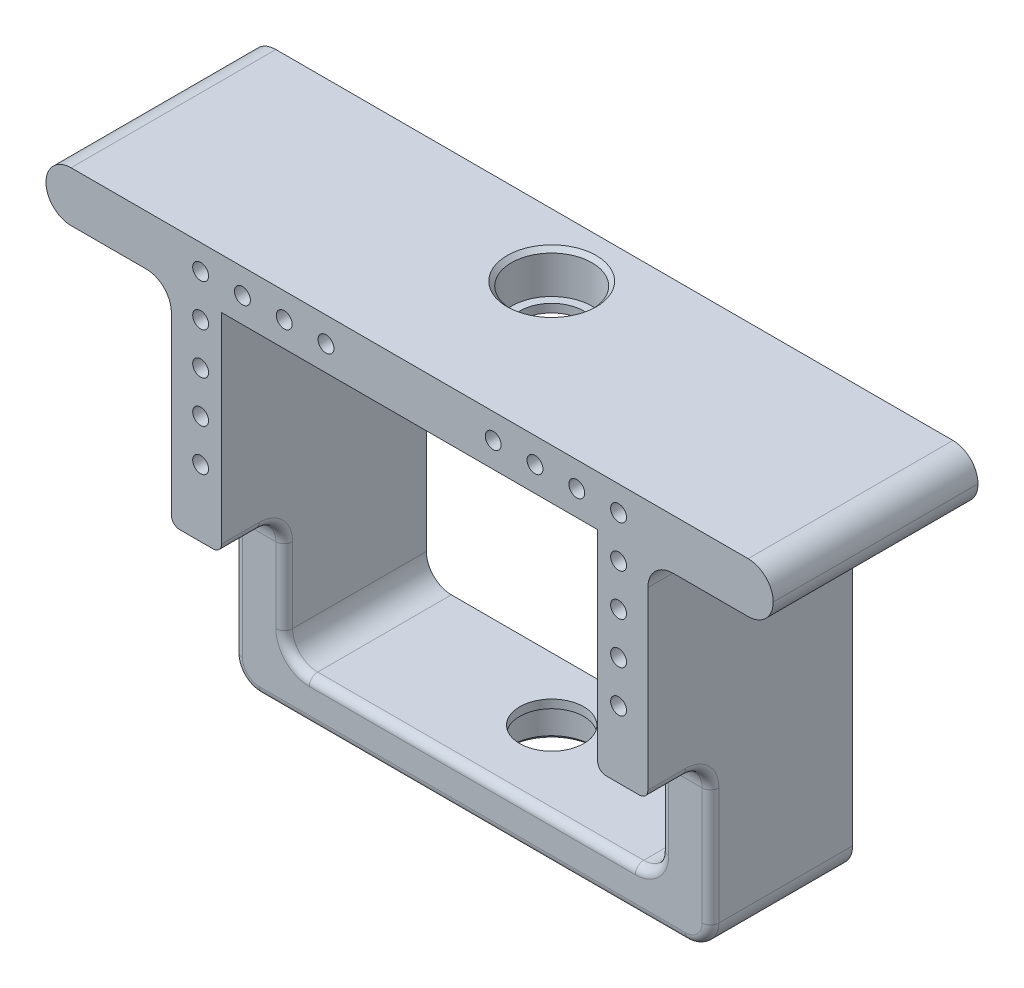
SolidWorks part; units mm, degrees
ref_plane "Plan de face" through (0, 0, 0) normal (0, 0, 1) x (1, 0, 0)
ref_plane "Plan de dessus" through (0, 0, 0) normal (0, 1, 0) x (1, 0, 0)
ref_plane "Plan de droite" through (0, 0, 0) normal (1, 0, 0) x (0, 0, -1)
sketch "Esquisse1" plane through (0, 0, 0) normal (0, 0, 1) x (1, 0, 0)
  line L1 (0, 0) -> (114, 0)
  line L2 (0, 0) -> (0, -102)
  line L3 (0, -102) -> (114, -102)
  line L4 (114, 0) -> (114, -102)
  line L5 (12, -12) -> (102, -12)
  line L6 (12, -12) -> (12, -92)
  line L7 (12, -92) -> (102, -92)
  line L8 (102, -12) -> (102, -92)
  dimension "D1" = 80
  dimension "D2" = 12
  dimension "D3" = 12
  dimension "D4" = 12
  dimension "D5" = 10
  dimension "D6" = 90
extrude "Boss.-Extru.1" add sketch "Esquisse1" along normal blind 49
sketch "Esquisse2" plane through (0, 0, 49) normal (0, 0, 1) x (1, 0, 0)
  line L0 (114, -102) -> (114, 0) construction
  line L1 (0, -102) -> (114, -102)
  line L2 (0, -102) -> (0, -62)
  line L3 (0, -62) -> (114, -62)
  line L4 (114, -102) -> (114, -62)
  dimension "D1" = 40
extrude "Enlèv. mat.-Extru.1" cut sketch "Esquisse2" against normal blind 15
sketch "Esquisse3" plane through (0, 0, 49) normal (0, 0, 1) x (1, 0, 0)
  line L0 (57, 0) -> (57, -12) construction
  line L1 (114, 0) -> (0, 0) construction
  line L2 (102, -12) -> (12, -12) construction
  line L3 (-28.1553, -6) -> (136.1205, -6) construction
  circle A0 centre (57, -6) radius 1.9 construction
  circle A1 centre (67, -6) radius 1.9 construction
  circle A2 centre (77, -6) radius 1.9
  circle A3 centre (87, -6) radius 1.9
  circle A4 centre (97, -6) radius 1.9
  circle A5 centre (107, -6) radius 1.9
  circle A6 centre (47, -6) radius 1.9 construction
  circle A7 centre (37, -6) radius 1.9
  circle A8 centre (27, -6) radius 1.9
  circle A9 centre (17, -6) radius 1.9
  circle A10 centre (7, -6) radius 1.9
  circle A11 centre (7, -16) radius 1.9
  circle A12 centre (107, -16) radius 1.9
  circle A13 centre (7, -26) radius 1.9
  circle A14 centre (107, -26) radius 1.9
  circle A15 centre (7, -36) radius 1.9
  circle A16 centre (107, -36) radius 1.9
  circle A17 centre (7, -46) radius 1.9
  circle A18 centre (107, -46) radius 1.9
  point P8 (57, -6)
  dimension "D1" = 3.8
  dimension "D2" = 6
  dimension "D3" = 6
  dimension "D4" = 5
extrude "Enlèv. mat.-Extru.2" cut sketch "Esquisse3" against normal through all
sketch "Esquisse4" plane through (0, 0, 0) normal (0, 0, -1) x (-1, 0, 0)
  circle A0 centre (-107, -6) radius 4
  circle A1 centre (-87, -6) radius 4
  circle A2 centre (-67, -6) radius 4 construction
  circle A3 centre (-47, -6) radius 4 construction
  circle A4 centre (-27, -6) radius 4
  circle A5 centre (-7, -6) radius 4
  circle A6 centre (-87, -26) radius 4
  circle A7 centre (-67, -26) radius 4
  circle A8 centre (-47, -26) radius 4
  circle A9 centre (-27, -26) radius 4
  circle A10 centre (-7, -26) radius 4
  circle A11 centre (-87, -46) radius 4
  circle A12 centre (-67, -46) radius 4
  circle A13 centre (-47, -46) radius 4
  circle A14 centre (-27, -46) radius 4
  circle A15 centre (-7, -46) radius 4
  circle A16 centre (-107, -26) radius 4
  circle A17 centre (-107, -46) radius 4
  circle A18 centre (-87, -6) radius 1.9 construction
  circle A19 centre (-107, -26) radius 1.9 construction
  point P3 (0, 0)
  dimension "D1" = 8
  dimension "D2" = 6
  dimension "D3" = 3
extrude "Enlèv. mat.-Extru.3" cut sketch "Esquisse4" against normal offset from surface (39 mm away) 10 up to face at (88.9, -6, 49)
sketch "Esquisse5" plane through (0, 0, 0) normal (0, 0, -1) x (-1, 0, 0)
  line L0 (-12, -12) -> (-102, -12) construction
  line L1 (0, 0) -> (30, 0)
  line L2 (0, 0) -> (0, -12)
  line L3 (0, -12) -> (30, -12)
  line L4 (30, 0) -> (30, -12)
  line L5 (-114, 0) -> (-144, 0)
  line L6 (-114, 0) -> (-114, -12)
  line L7 (-114, -12) -> (-144, -12)
  line L8 (-144, 0) -> (-144, -12)
  dimension "D1" = 30
  dimension "D2" = 30
extrude "Boss.-Extru.2" add sketch "Esquisse5" against normal up to vertex (49 mm away) up to point (0, 0, 49)
sketch "Esquisse6" plane through (0, 0, 0) normal (0, 1, 0) x (1, 0, 0)
  line L0 (-30, -15) -> (144, -15) construction
  line L1 (-30, -49) -> (-30, 0) construction
  line L2 (144, -49) -> (144, 0) construction
  line L3 (144, -49) -> (-30, -49) construction
  line L4 (57, -49) -> (57, 0) construction
  line L5 (0, 0) -> (114, 0) construction
  circle A0 centre (57, -15) radius 7.65
  dimension "D2" = 15.3
  dimension "D1" = 34
extrude "Enlèv. mat.-Extru.4" cut sketch "Esquisse6" against normal through all
sketch "Esquisse7" plane through (0, 0, 0) normal (0, 1, 0) x (1, 0, 0)
  circle A0 centre (57, -15) radius 9.65
  dimension "D1" = 19.3
extrude "Enlèv. mat.-Extru.5" cut sketch "Esquisse7" against normal offset from surface (10 mm away) 2 up to face at (57, -12, 7.35)
extrude "Enlèv. mat.-Extru.6" cut sketch "Esquisse7<2>" along normal offset from surface (8 mm away) 2 from surface up to face at (57, -92, 22.65) starting at face at (57, -102, 22.65)
sketch "Esquisse7<2>" plane through (0, 0, 0) normal (0, 1, 0) x (1, 0, 0) same geometry as "Esquisse7"
fillet "Congé1" radius 6 12 edges at (144, -12, 24.5) (144, 0, 24.5) (-30, 0, 24.5) (-30, -12, 24.5) (0, -102, 17) (12, -92, 17) (102, -92, 17) (114, -102, 17) (114, -12, 24.5) (6, -62, 34) (108, -62, 34) (0, -12, 24.5)
chamfer "Chanfrein1" distance 1 angle 45 2 edges at (57, -102, 24.65) (57, 0, 24.65)
sketch "Esquisse8" plane through (0, -102, 0) normal (0, -1, 0) x (1, 0, 0)
  text T0 "IUT GEII Toulon - Robot Club Toulonnais" font "Century Gothic" height 3.75
  point P1 (9.7545, 26.8213)
  point P2 (0, 0)
  point P3 (0, 0)
  point P4 (10.6614, 25.0637)
  point P5 (0, 0)
  point P6 (0, 0)
  point P7 (0, 0)
extrude "Enlèv. mat.-Extru.7" cut sketch "Esquisse8" against normal blind 1
fillet "Congé2" radius 2 18 edges at (12, -62, 44.5) (12, -63.7574, 35.7574) (12, -77, 34) (13.7574, -90.2426, 34) (57, -92, 34) (100.2426, -90.2426, 34) (102, -77, 34) (102, -63.7574, 35.7574) (0, -62, 44.5) (0, -63.7574, 35.7574) (0, -82, 34) (1.7574, -100.2426, 34) (57, -102, 34) (112.2426, -100.2426, 34) (114, -82, 34) (114, -63.7574, 35.7574) (102, -62, 44.5) (114, -62, 44.5)
